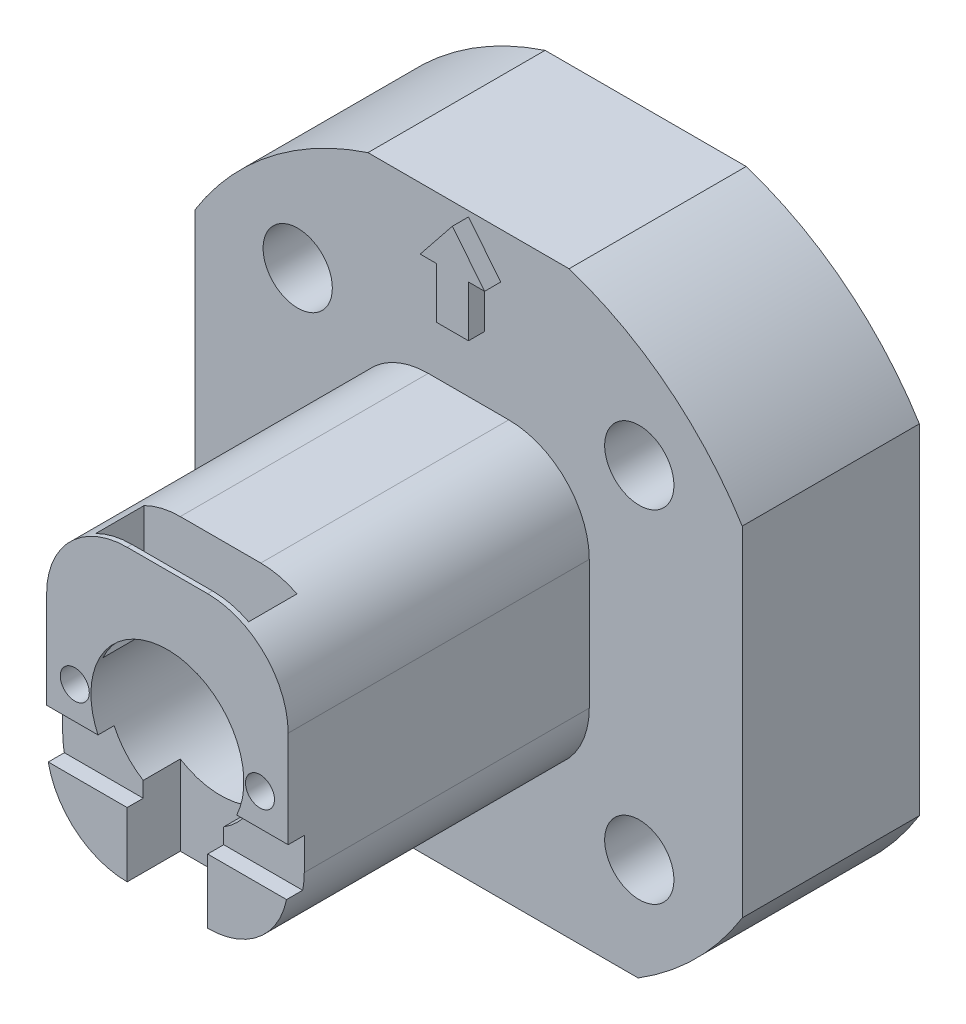
SolidWorks part; units mm, degrees
ref_plane "Front Plane" through (0, 0, 0) normal (0, 0, 1) x (1, 0, 0)
ref_plane "Top Plane" through (0, 0, 0) normal (0, 1, 0) x (1, 0, 0)
ref_plane "Right Plane" through (0, 0, 0) normal (1, 0, 0) x (0, 0, -1)
sketch "Sketch1" plane through (0, 0, 0) normal (0, 0, 1) x (1, 0, 0)
  circle A0 centre (0, 0) radius 20
  circle A1 centre (0, 0) radius 4.75
  dimension "D1" = 9.5
  dimension "D2" = 40
extrude "Boss-Extrude1" add sketch "Sketch1" along normal blind 11
sketch "Sketch2" plane through (0, 0, 11) normal (0, 0, 1) x (1, 0, 0)
  line L0 (0, 0) -> (0, 19) construction
  line L1 (-6.5933, 20) -> (6.5933, 20)
  line L2 (-6.5933, 20) -> (-6.5933, 19)
  line L3 (-6.5933, 19) -> (6.5933, 19)
  line L4 (6.5933, 20) -> (6.5933, 19)
  line L6 (-20, 15.8908) -> (-17, 15.8908)
  line L7 (-20, 15.8908) -> (-20, -10.5357)
  line L8 (-20, -10.5357) -> (-17, -10.5357)
  line L9 (-17, 15.8908) -> (-17, -10.5357)
  line L10 (20, 11.7256) -> (17, 11.7256)
  line L11 (20, 11.7256) -> (20, -14.8962)
  line L12 (20, -14.8962) -> (17, -14.8962)
  line L13 (17, 11.7256) -> (17, -14.8962)
  line L14 (21.7417, -20) -> (-18.9444, -20)
  line L15 (21.7417, -20) -> (21.7417, -17)
  line L16 (21.7417, -17) -> (-18.9444, -17)
  line L17 (-18.9444, -20) -> (-18.9444, -17)
  circle A0 centre (0, 0) radius 20 construction
  dimension "D1" = 1
  dimension "D2" = 3
extrude "Cut-Extrude1" cut sketch "Sketch2" against normal through all
sketch "Sketch3" plane through (0, 0, 11) normal (0, 0, 1) x (1, 0, 0)
  circle A0 centre (10.6066, -10.6066) radius 2 construction
  circle A1 centre (10.6066, 10.6066) radius 2 construction
  circle A2 centre (-10.6066, -10.6066) radius 2 construction
  circle A3 centre (-10.6066, 10.6066) radius 2 construction
  circle A4 centre (10.6066, -10.6066) radius 2 construction
  circle A5 centre (10.6066, 10.6066) radius 2 construction
  circle A6 centre (-10.6066, -10.6066) radius 2 construction
  circle A7 centre (-10.6066, 10.6066) radius 2 construction
  circle A8 centre (-10.6066, -10.6066) radius 2.15
  circle A9 centre (-10.6066, 10.6066) radius 2.15
  circle A10 centre (10.6066, 10.6066) radius 2.15
  circle A11 centre (10.6066, -10.6066) radius 2.15
  dimension "D1" = 4.3
extrude "Cut-Extrude2" cut sketch "Sketch3" against normal through all
sketch "Sketch5" plane through (0, 0, 11) normal (0, 0, 1) x (1, 0, 0)
  line L0 (0, 9) -> (0, -9) construction
  line L8 (7.5, -4) -> (7.5, 4)
  line L9 (2.5, 9) -> (-2.5, 9)
  line L10 (-7.5, 4) -> (-7.5, -4)
  line L11 (-2.5, -9) -> (2.5, -9)
  circle A0 centre (-5.75, 0) radius 1.075 construction
  circle A1 centre (5.75, 0) radius 1.075 construction
  circle A2 centre (-5.75, 0) radius 1.075 construction
  circle A3 centre (5.75, 0) radius 1.075 construction
  circle A4 centre (-5.75, 0) radius 0.9
  circle A5 centre (5.75, 0) radius 0.9
  arc A12 (2.5, -9) -> (7.5, -4) centre (2.5, -4) ccw
  arc A13 (7.5, 4) -> (2.5, 9) centre (2.5, 4) ccw
  arc A14 (-2.5, 9) -> (-7.5, 4) centre (-2.5, 4) ccw
  arc A15 (-7.5, -4) -> (-2.5, -9) centre (-2.5, -4) ccw
  dimension "D2" = 1.8
  dimension "D4" = 5
  dimension "D1" = 18
  dimension "D3" = 15
extrude "Boss-Extrude2" add sketch "Sketch5" along normal up to surface (18.7 mm away)
sketch "Sketch13" plane through (0, 0, 11) normal (0, 0, 1) x (1, 0, 0)
  circle A0 centre (5.75, 0) radius 0.9 construction
  circle A1 centre (-5.75, 0) radius 0.9 construction
  circle A2 centre (5.75, 0) radius 0.9
  circle A3 centre (-5.75, 0) radius 0.9
extrude "Boss-Extrude3" add sketch "Sketch13" along normal offset from surface (8.7 mm away) 10 up to face at (5.75, -0.9, 29.7)
sketch "Sketch7" plane through (0, 0, 29.7) normal (0, 0, 1) x (1, 0, 0)
  line L1 (-40.6618, -2) -> (27.6064, -2)
  line L2 (-40.6618, -2) -> (-40.6618, -5)
  line L3 (-40.6618, -5) -> (27.6064, -5)
  line L4 (27.6064, -2) -> (27.6064, -5)
  dimension "D1" = 3
  dimension "D2" = 2
extrude "Cut-Extrude4" cut sketch "Sketch7" against normal blind 1
sketch "Sketch10" plane through (0, 0, 0) normal (0, 0, -1) x (-1, 0, 0)
  circle A0 centre (0, 0) radius 4.75 construction
  circle A1 centre (0, 0) radius 4.75
extrude "Cut-Extrude6" cut sketch "Sketch10" against normal through all
sketch "Sketch11" plane through (0, 9, 0) normal (0, 1, 0) x (1, 0, 0)
  line L1 (-4.75, -29.4) -> (4.75, -29.4)
  line L2 (-4.75, -29.4) -> (-4.75, -26.4)
  line L3 (-4.75, -26.4) -> (4.75, -26.4)
  line L4 (4.75, -29.4) -> (4.75, -26.4)
  line L5 (0, 0) -> (0, -26.4) construction
  line L6 (-6.245, 0) -> (6.245, 0) construction
  dimension "D1" = 3
  dimension "D2" = 9.5
extrude "Cut-Extrude7" cut sketch "Sketch11" against normal blind 7
sketch "Sketch12" plane through (0, 0, 0) normal (0, 0, -1) x (-1, 0, 0)
  circle A0 centre (0, 0) radius 6
  dimension "D1" = 12
extrude "Cut-Extrude8" cut sketch "Sketch12" against normal offset from surface (14.7 mm away) 15 up to face at (0, 3.3526, 29.7)
chamfer "Chamfer2" distance 1.5 angle 45 1 edges at (0, -6, 14.7)
chamfer "Chamfer1" distance 4 angle 50 1 edges at (-6, 0, 0) first distance on face at (-6, 0, 0)
fillet "Fillet2" radius 10 2 edges at (4.75, 2, 27.9) (-4.75, 2, 27.9)
sketch "Sketch14" plane through (0, -9, 0) normal (0, -1, 0) x (1, 0, 0)
  line L0 (2.5, 29.7) -> (2.5, 11) construction
  line L1 (-2.5, 29.7) -> (2.5, 29.7)
  line L2 (-2.5, 29.7) -> (-2.5, 26.4)
  line L3 (-2.5, 26.4) -> (2.5, 26.4)
  line L4 (2.5, 29.7) -> (2.5, 26.4)
  line L5 (2.5, 26.4) -> (-2.5, 26.4) construction
extrude "Cut-Extrude9" cut sketch "Sketch14" against normal blind 10
sketch "Sketch15" plane through (0, 0, 11) normal (0, 0, 1) x (1, 0, 0)
  line L0 (-1, 13.002) -> (1, 13.002)
  line L1 (1, 13.002) -> (1, 16.1642)
  line L2 (1, 16.1642) -> (2, 16.1642)
  line L3 (2, 16.1642) -> (0, 18.6642)
  line L4 (0, 18.6642) -> (-2, 16.1642)
  line L5 (-2, 16.1642) -> (-1, 16.1642)
  line L6 (-1, 16.1642) -> (-1, 13.002)
  line L7 (0, 0) -> (0, 13.002) construction
  dimension "D1" = 2
  dimension "D2" = 4
  dimension "D3" = 2.5
extrude "Boss-Extrude4" add sketch "Sketch15" along normal blind 1
